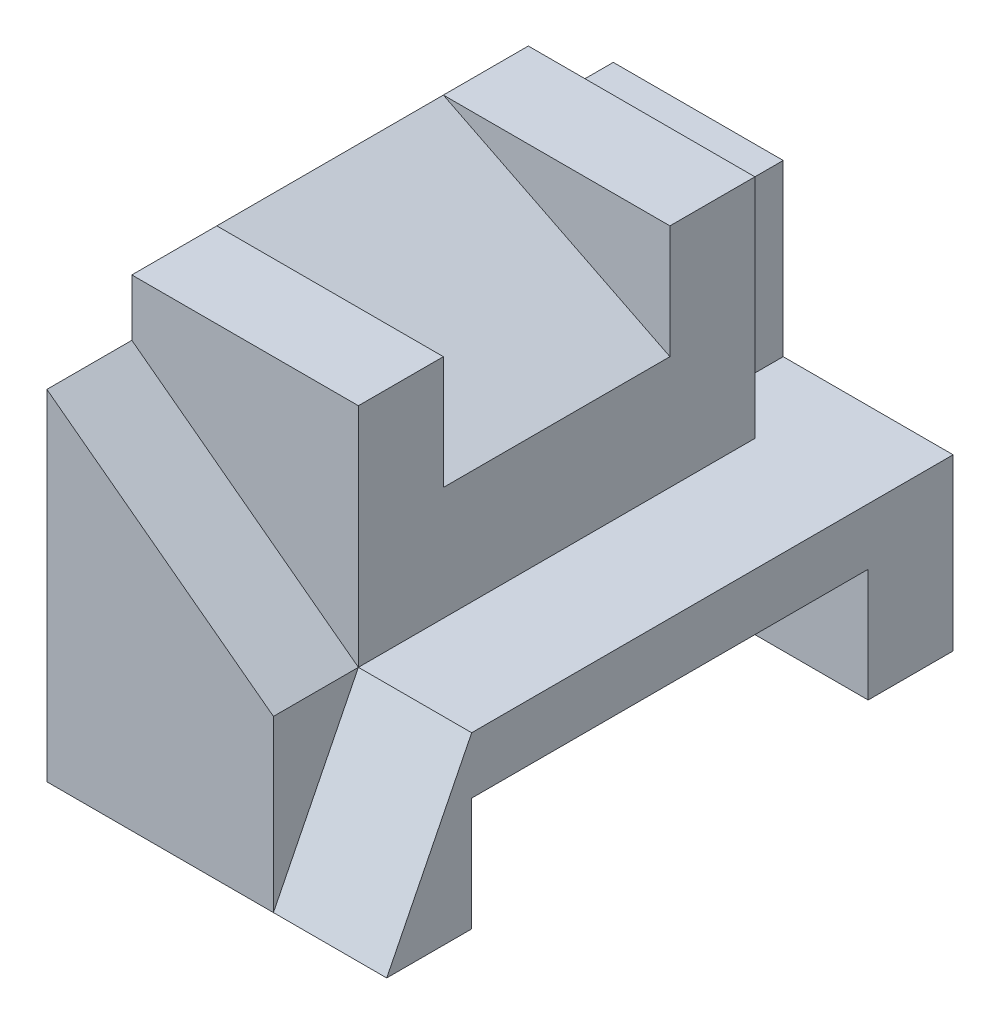
SolidWorks part; units mm, degrees
ref_plane "Alzado" through (0, 0, 0) normal (0, 0, 1) x (1, 0, 0)
ref_plane "Planta" through (0, 0, 0) normal (0, 1, 0) x (1, 0, 0)
ref_plane "Vista lateral" through (0, 0, 0) normal (1, 0, 0) x (0, 0, -1)
sketch "Croquis1" plane through (0, 0, 0) normal (1, 0, 0) x (0, 0, -1)
  line L0 (0, 0) -> (0, 2)
  line L1 (0, 2) -> (-7, 2)
  line L2 (-7, 2) -> (-7, 0)
  line L3 (-7, 0) -> (-8.5, 0)
  line L4 (-8.5, 0) -> (-8.5, 3)
  line L5 (-8.5, 3) -> (1.5, 3)
  line L6 (1.5, 3) -> (1.5, 0)
  line L7 (1.5, 0) -> (0, 0)
  dimension "D1" = 1.5
  dimension "D2" = 7
  dimension "D3" = 10
  dimension "D4" = 2
  dimension "D5" = 3
extrude "Saliente-Extruir1" add sketch "Croquis1" against normal blind 2
chamfer "Chaflán2" distance 3 distance2 1.5 1 edges at (-1, 3, 8.5) first distance on face at (-1, 1.5, 8.5)
sketch "Croquis2" plane through (-2, 0, 0) normal (-1, 0, 0) x (0, 0, 1)
  line L0 (7, 3) -> (8.5, 3)
  line L1 (8.5, 3) -> (8.5, 0)
  line L8 (7, 0) -> (8.5, 0)
  line L9 (8.5, 0) -> (7, 3)
  line L10 (7, 3) -> (-1.5, 3)
  line L11 (-1.5, 3) -> (-1.5, 0)
  line L12 (-1.5, 0) -> (0, 0)
  line L13 (0, 0) -> (0, 2)
  line L14 (0, 2) -> (7, 2)
  line L15 (7, 2) -> (7, 0)
  line L16 (7, 0) -> (8.5, 0)
  line L18 (7, 3) -> (-1.5, 3)
  line L19 (-1.5, 3) -> (-1.5, 0)
  line L20 (-1.5, 0) -> (0, 0)
  line L21 (0, 0) -> (0, 2)
  line L22 (0, 2) -> (7, 2)
  line L23 (7, 2) -> (7, 0)
  dimension "D1" = 0
extrude "Saliente-Extruir2" add sketch "Croquis2" along normal blind 4
sketch "Croquis3" plane through (0, 3, 0) normal (0, 1, 0) x (1, 0, 0)
  line L0 (-2, -7) -> (-6, -7)
  line L6 (0, 1.5) -> (-6, 1.5)
  line L7 (-6, 1.5) -> (-6, -8.5)
  line L8 (-6, -8.5) -> (-2, -8.5)
  line L9 (-2, -8.5) -> (-2, -7)
  line L10 (-2, -7) -> (0, -7)
  line L11 (0, -7) -> (0, 1.5)
  line L13 (-6, -7) -> (-6, -8.5)
  line L14 (-6, -8.5) -> (-2, -8.5)
  line L15 (-2, -8.5) -> (-2, -7)
  dimension "D1" = 0
extrude "Saliente-Extruir3" add sketch "Croquis3" along normal blind 3
chamfer "Chaflán3" distance 3 distance2 4 1 edges at (-2, 6, 7.75) first distance on face at (-2, 3.75, 7.75)
sketch "Croquis4" plane through (-2, 0, 0) normal (1, 0, 0) x (0, 0, -1)
  line L4 (1.5, 3) -> (-7, 3) construction
  line L16 (1.5, 3) -> (-7, 3)
  line L24 (-7, 7) -> (-5.5, 7)
  line L25 (-5.5, 7) -> (-5.5, 5)
  line L26 (-5.5, 5) -> (-1.5, 5)
  line L27 (-1.5, 5) -> (-1.5, 7)
  line L28 (-1.5, 7) -> (0, 7)
  line L29 (0, 7) -> (0, 3)
  line L30 (-7, 7) -> (-7, 3)
  dimension "D1" = 1.5
  dimension "D2" = 4
  dimension "D3" = 1.5
  dimension "D4" = 2
  dimension "D5" = 4
  dimension "D6" = 4
extrude "Saliente-Extruir4" add sketch "Croquis4" against normal blind 4 contours L24 L30 L16 L29 L28 L27 L26 L25 region at (-2, 4.6, 3.5)
sketch "Croquis5" plane through (0, 5, 0) normal (0, 1, 0) x (1, 0, 0)
  line L4 (-2, -5.5) -> (-2, -1.5)
  line L5 (-2, -1.5) -> (-6, -1.5)
  line L6 (-6, -1.5) -> (-6, -5.5)
  line L7 (-6, -5.5) -> (-2, -5.5)
  line L8 (-2, -5.5) -> (-2, -1.5)
  line L9 (-2, -1.5) -> (-6, -1.5)
  line L10 (-6, -1.5) -> (-6, -5.5)
  line L11 (-6, -5.5) -> (-2, -5.5)
  dimension "D1" = 0
extrude "Saliente-Extruir5" add sketch "Croquis5" along normal blind 2 separate body contours L8 L9 L10 L11
chamfer "Chaflán4" distance 2 distance2 4 1 edges at (-2, 7, 3.5) first distance on face at (-2, 6, 3.5)
sketch "Croquis6" plane through (0, 3, 0) normal (0, 1, 0) x (1, 0, 0)
  line L0 (-3, 1.5) -> (-3, 0)
  line L6 (-6, 1.5) -> (-6, 0)
  line L7 (-6, 0) -> (-2, 0)
  line L8 (-2, 0) -> (-2, -7)
  line L9 (-2, -7) -> (0, -7)
  line L10 (0, -7) -> (0, 1.5)
  line L11 (0, 1.5) -> (-6, 1.5)
  line L12 (-6, 1.5) -> (-6, 0)
  line L13 (-6, 0) -> (-3, 0)
  line L17 (-3, 1.5) -> (-6, 1.5)
  dimension "D2" = 3
  dimension "D1" = 0
extrude "Saliente-Extruir6" add sketch "Croquis6" along normal blind 3 contours L12 L13 L0 L17
